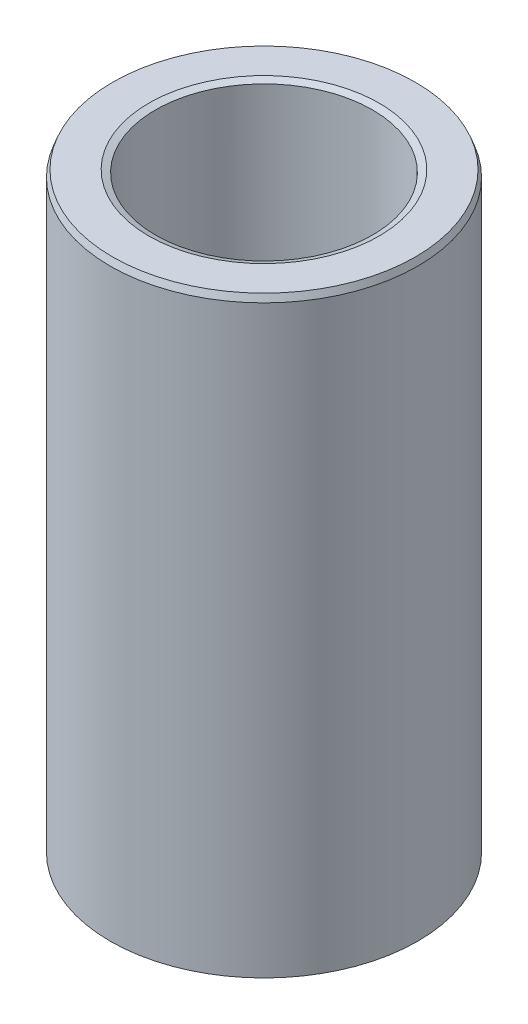
SolidWorks part; units mm, degrees
ref_plane "Front Plane" through (0, 0, 0) normal (0, 0, 1) x (1, 0, 0)
ref_plane "Top Plane" through (0, 0, 0) normal (0, 1, 0) x (1, 0, 0)
ref_plane "Right Plane" through (0, 0, 0) normal (1, 0, 0) x (0, 0, -1)
sketch "Sketch1" plane through (0, 0, 0) normal (0, 1, 0) x (1, 0, 0)
  circle A0 centre (0, 0) radius 35
  dimension "SLEEVE_OD" = 70
extrude "Boss-Extrude1" add sketch "Sketch1" along normal blind 135.0899
sketch "Sketch2" plane through (0, 0, 0) normal (0, 1, 0) x (1, 0, 0)
  circle A0 centre (0, 0) radius 24.6821
  dimension "BORE_D" = 49.3643
extrude "Cut-Extrude1" cut sketch "Sketch2" along normal through all
chamfer "Chamfer1" distance 1.5187 angle 20.458 4 edges at (0, 135.0899, 24.6821) (0, 0, 24.6821) (0, 0, 35) (0, 135.0899, 35) first distance on face at (0, 135.0899, 24.6821) first distance on face at (0, 0, 24.6821) first distance on face at (0, 135.0899, 35)
